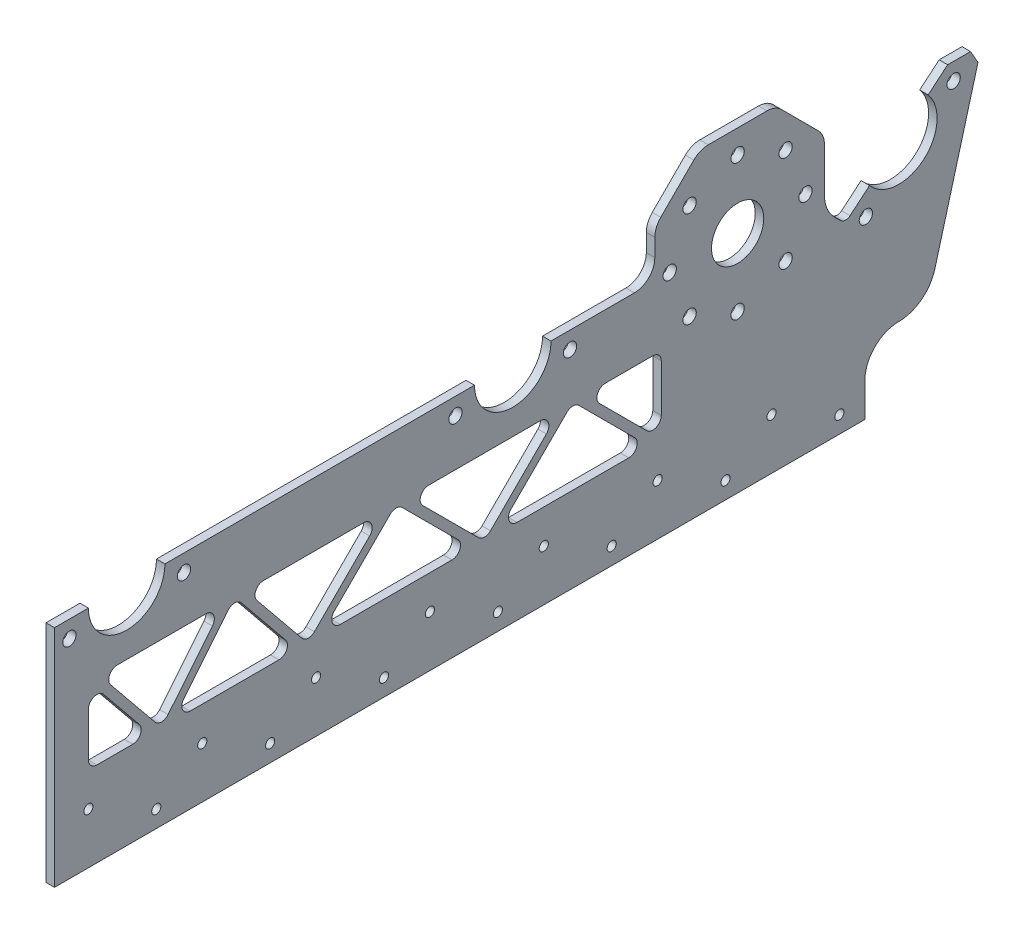
SolidWorks part; units mm, degrees
material "6061 Alloy"
ref_plane "Front Plane" through (0, 0, 0) normal (0, 0, 1) x (1, 0, 0)
ref_plane "Top Plane" through (0, 0, 0) normal (0, 1, 0) x (1, 0, 0)
ref_plane "Right Plane" through (0, 0, 0) normal (1, 0, 0) x (0, 0, -1)
sketch "Sketch1" plane through (0, 0, 0) normal (1, 0, 0) x (0, 0, -1)
  line L0 (-12.7, -12.7) -> (-315.9379, -12.7)
  line L1 (-315.9379, -12.7) -> (-315.9379, 71.4629)
  line L2 (-315.9379, 71.4629) -> (-303.2379, 71.4629)
  line L3 (-274.6121, 71.4629) -> (-158.7754, 71.4629)
  line L5 (10.9643, 80.6631) -> (18.2626, 86.7871)
  line L7 (-315.9379, 12.7) -> (13.4731, 12.7) construction
  line L8 (-12.7, -12.7) -> (-12.7, 0)
  line L9 (0, 12.4079) -> (0, 12.7) construction
  line L10 (13.4731, 22.9772) -> (30.9626, 86.7871)
  line L12 (-10.9643, 62.2627) -> (10.9643, 80.6631) construction
  line L13 (18.2626, 86.7871) -> (30.9626, 86.7871)
  line L14 (-130.1496, 71.4629) -> (-91.313, 71.4629)
  line L15 (-10.9643, 62.2627) -> (-18.2626, 56.1387)
  line L16 (-21.6532, 56.2511) -> (-23.945, 58.4485)
  line L18 (0, 71.4629) -> (-144.4625, 71.4629) construction
  line L19 (-315.9379, 15.875) -> (13.4731, 15.875) construction
  line L20 (-27.8553, 67.6154) -> (-27.8553, 87.307)
  line L21 (-27.8553, 87.307) -> (-46.1742, 105.6259)
  line L22 (-46.1742, 105.6259) -> (-74.4758, 105.6259)
  line L23 (-91.313, 88.7887) -> (-91.313, 71.4629)
  line L25 (-74.4758, 105.6259) -> (-91.313, 88.7887)
  line L26 (-144.4625, 71.4629) -> (-288.925, 71.4629) construction
  arc A3 (0, 12.7) -> (13.4731, 22.9772) centre (0, 26.67) ccw
  arc A4 (0, 12.7) -> (-12.7, 0) centre (0, 0) ccw
  circle A5 centre (0, 0) radius 12.4079 construction
  arc A6 (-303.2379, 71.4629) -> (-274.6121, 71.4629) centre (-288.925, 71.4629) ccw
  arc A7 (-158.7754, 71.4629) -> (-130.1496, 71.4629) centre (-144.4625, 71.4629) ccw
  arc A8 (-10.9643, 62.2627) -> (10.9643, 80.6631) centre (0, 71.4629) ccw
  arc A9 (-18.2626, 56.1387) -> (-21.6532, 56.2511) centre (-19.8953, 58.0845) cw
  circle A11 centre (-60.325, 71.4629) radius 9.779
  arc A14 (-27.8553, 67.6154) -> (-23.945, 58.4485) centre (-15.1553, 67.6154) ccw
  circle A15 centre (-60.325, 71.4629) radius 25.4 construction
  circle A16 centre (-60.325, 96.8629) radius 2.413
  circle A17 centre (-42.3645, 89.4234) radius 2.413
  circle A18 centre (-34.925, 71.4629) radius 2.413
  circle A19 centre (-42.3645, 53.5024) radius 2.413
  circle A20 centre (-60.325, 46.0629) radius 2.413
  circle A21 centre (-78.2855, 53.5024) radius 2.413
  circle A22 centre (-85.725, 71.4629) radius 2.413
  circle A23 centre (-78.2855, 89.4234) radius 2.413
  point P4 (-164.319, -12.7)
  point P44 (-82.018, 71.4629)
  point P51 (-27.8553, 62.1979)
  point P60 (-60.325, 71.4629)
  dimension "D1" = 25.4
  dimension "D3" = 12.7
  dimension "D5" = 28.6258
  dimension "D6" = 3.175
  dimension "D7" = 13.97
  dimension "D8" = 12.7
  dimension "D10" = 24.8158
  dimension "D13" = 9.5273
  dimension "D14" = 140
  dimension "D15" = 2.54
  dimension "D16" = 50.8
  dimension "D17" = 60.325
  dimension "D18" = 41.275
  dimension "D24" = 3.175
  dimension "D26" = 12.7
  dimension "D19" = 4.826
  dimension "D25" = 6.35
  dimension "D29" = 6.35
  dimension "D20" = 4.6567
  dimension "D30" = 9.779
  dimension "D2" = 0
  dimension "D4" = 12.7
  dimension "D9" = 12.7
  dimension "D11" = 288.925
  dimension "D12" = 288.925
  dimension "D21" = 8
  dimension "D22" = 45
  dimension "D23" = 45
  dimension "D27" = 6.35
  dimension "D28" = 3.175
extrude "Boss-Extrude1" add sketch "Sketch1" along normal blind 3.175
hole_wizard "#10 Clearance Hole1" positions "Sketch2" profile "Sketch3" hole size "#10" standard "ANSI Inch" end condition through all
sketch "Sketch2" plane through (3.175, 0, 0) normal (1, 0, 0) x (0, 0, -1)
  line L0 (-310.3562, 65.1129) -> (-267.4937, 65.1129) construction
  line L2 (-165.8937, 65.1129) -> (-123.0313, 65.1129) construction
  line L4 (-12.3356, 52.8228) -> (20.499, 80.3743) construction
  line L6 (-303.2379, 71.4629) -> (-315.9379, 71.4629) construction
  line L7 (-288.925, 65.1129) -> (-288.925, 71.4629) construction
  line L9 (-144.4625, 71.4629) -> (-144.4625, 65.1129) construction
  line L11 (0, 71.4629) -> (4.0817, 66.5985) construction
  line L14 (18.2626, 86.7871) -> (10.9643, 80.6631) construction
  line L15 (18.2626, 86.7871) -> (10.9643, 80.6631) construction
  point P0 (-310.3562, 65.1129)
  point P2 (-267.4937, 65.1129)
  point P4 (-165.8937, 65.1129)
  point P6 (-123.0313, 65.1129)
  point P8 (-12.3356, 52.8228)
  point P10 (20.499, 80.3743)
  dimension "D1" = 42.8625
  dimension "D2" = 6.35
  dimension "D3" = 6.35
sketch "Sketch3" plane through (3.175, 65.1129, 310.3562) normal (0, 1, 0) x (0, 0, -1)
  line L0 (0, 0) -> (0, 3.175)
  line L1 (0, 3.175) -> (2.4892, 3.175)
  line L2 (2.4892, 3.175) -> (2.4892, 0)
  line L5 (2.4892, 0) -> (0, 0)
  line L11 (0, -6.35) -> (0, 107.95) construction
  dimension "Thru Hole Dia." = 4.9784
  dimension "Thru Hole Depth" = 3.175
hole_wizard "#10 Clearance Hole2" positions "Sketch5" profile "Sketch6" hole size "#10" standard "ANSI Inch"
sketch "Sketch5" plane through (3.175, 0, 0) normal (1, 0, 0) x (0, 0, -1)
  point P0 (-60.325, 96.8629)
  point P3 (-42.3645, 89.4234)
  point P6 (-34.925, 71.4629)
  point P9 (-42.3645, 53.5024)
  point P12 (-60.325, 46.0629)
  point P15 (-78.2855, 53.5024)
  point P18 (-85.725, 71.4629)
  point P21 (-78.2855, 89.4234)
sketch "Sketch6" plane through (3.175, 96.8629, 60.325) normal (0, 1, 0) x (0, 0, -1)
  line L0 (0, 0) -> (0, 4.6707)
  line L1 (0, 4.6707) -> (2.4892, 3.175)
  line L2 (2.4892, 3.175) -> (2.4892, 0)
  line L5 (2.4892, 0) -> (0, 0)
  line L10 (0, 4.6707) -> (-2.4892, 3.175) construction
  line L11 (0, -6.35) -> (0, 107.95) construction
  dimension "Hole Dia." = 4.9784
  dimension "Hole Depth" = 3.175
  dimension "Drill Angle" = 118
chamfer "Chamfer1" distance 5.08 angle 45 1 edges at (1.5875, 86.7871, -30.9626) first distance on face at (1.5875, 54.8821, -22.2179)
fillet "Fillet1" radius 7.62 5 edges at (1.5875, 87.307, 27.8553) (1.5875, 105.6259, 46.1742) (1.5875, 105.6259, 74.4758) (1.5875, 88.7887, 91.313) (1.5875, 71.4629, 91.313)
hole_wizard "1/8 (0.135) Diameter Hole1" positions "Sketch7" profile "Sketch8" hole size "1/8" standard "ANSI Inch"
sketch "Sketch7" plane through (0, 0, 0) normal (-1, 0, 0) x (0, 0, 1)
  line L0 (315.9379, -12.7) -> (12.7, -12.7) construction
  line L1 (12.7, -12.7) -> (12.7, 0) construction
  line L2 (315.9379, 71.4629) -> (315.9379, -12.7) construction
  point P0 (22.2504, -6.35)
  point P2 (47.6504, 6.35)
  point P19 (64.8483, -6.35)
  point P20 (90.2483, 6.35)
  point P21 (107.4462, -6.35)
  point P22 (132.8462, 6.35)
  point P23 (150.0441, -6.35)
  point P24 (175.4441, 6.35)
  point P25 (192.6421, -6.35)
  point P26 (218.0421, 6.35)
  point P27 (235.24, -6.35)
  point P28 (260.64, 6.35)
  point P29 (277.8379, -6.35)
  point P30 (303.2379, 6.35)
  dimension "D1" = 6.35
  dimension "D2" = 25.4
  dimension "D3" = 12.7
  dimension "D4" = 9.5504
  dimension "D6" = 12.7
  dimension "D5" = 7
sketch "Sketch8" plane through (0, -6.35, 22.2504) normal (0, 1, 0) x (0, 0, 1)
  line L0 (0, 0) -> (0, 17.5402)
  line L1 (0, 17.5402) -> (1.7145, 16.51)
  line L2 (1.7145, 16.51) -> (1.7145, 0)
  line L5 (1.7145, 0) -> (0, 0)
  line L10 (0, 17.5402) -> (-1.7145, 16.51) construction
  line L11 (0, -6.35) -> (0, 107.95) construction
  dimension "Hole Dia." = 3.429
  dimension "Hole Depth" = 16.51
  dimension "Drill Angle" = 118
sketch "Sketch9" plane through (3.175, 0, 0) normal (1, 0, 0) x (0, 0, -1)
  line L0 (-303.2379, 47.625) -> (-303.2379, 19.05)
  line L1 (-303.2379, 19.05) -> (-279.973, 19.05)
  line L2 (-279.973, 19.05) -> (-303.2379, 47.625)
  line L3 (-315.9379, 12.7) -> (-12.7, 12.7) construction
  line L4 (-315.9379, 15.875) -> (-12.7, 15.875) construction
  line L5 (-299.1437, 47.625) -> (-275.8788, 19.05)
  line L6 (-275.8788, 19.05) -> (-252.6139, 47.625)
  line L7 (-252.6139, 47.625) -> (-299.1437, 47.625)
  line L8 (-271.7845, 19.05) -> (-248.5196, 47.625)
  line L9 (-248.5196, 47.625) -> (-225.2548, 19.05)
  line L10 (-225.2548, 19.05) -> (-271.7845, 19.05)
  line L11 (-244.4254, 47.625) -> (-221.1605, 19.05)
  line L12 (-221.1605, 19.05) -> (-192.5855, 47.625)
  line L13 (-192.5855, 47.625) -> (-244.4254, 47.625)
  line L14 (-216.6704, 19.05) -> (-188.0954, 47.625)
  line L15 (-188.0954, 47.625) -> (-159.5204, 19.05)
  line L16 (-159.5204, 19.05) -> (-216.6704, 19.05)
  line L17 (-183.6053, 47.625) -> (-155.0303, 19.05)
  line L18 (-155.0303, 19.05) -> (-126.4553, 47.625)
  line L19 (-126.4553, 47.625) -> (-183.6053, 47.625)
  line L20 (-121.9651, 47.625) -> (-150.5401, 19.05)
  line L21 (-150.5401, 19.05) -> (-93.3901, 19.05)
  line L22 (-93.3901, 19.05) -> (-121.9651, 47.625)
  line L32 (-315.9379, -12.7) -> (-12.7, -12.7) construction
  line L33 (-315.9379, 71.4629) -> (-315.9379, -12.7) construction
  line L35 (-117.475, 47.625) -> (-88.9, 19.05)
  line L36 (-88.9, 19.05) -> (-88.9, 47.625)
  line L37 (-88.9, 47.625) -> (-117.475, 47.625)
  line L38 (-12.7, -12.7) -> (-12.7, 0) construction
  arc A0 (-303.2379, 71.4629) -> (-274.6121, 71.4629) centre (-288.925, 71.4629) ccw construction
  point P28 (0, 0)
  dimension "D1" = 3.175
  dimension "D2" = 3.175
  dimension "D3" = 3.175
  dimension "D4" = 3.175
  dimension "D5" = 3.175
  dimension "D6" = 3.175
  dimension "D7" = 3.175
  dimension "D8" = 76.2
  dimension "D9" = 3.175
  dimension "D11" = 25.4
  dimension "D12" = 3.175
  dimension "D13" = 12.7
  dimension "D15" = 9.525
extrude "Cut-Extrude1" cut sketch "Sketch9" against normal through all
fillet "Fillet2" radius 3.175 24 edges at (1.5875, 19.05, 303.2379) (1.5875, 47.625, 303.2379) (1.5875, 19.05, 279.973) (1.5875, 19.05, 150.5401) (1.5875, 47.625, 121.9651) (1.5875, 19.05, 93.3901) (1.5875, 19.05, 155.0303) (1.5875, 47.625, 183.6053) (1.5875, 47.625, 126.4553) (1.5875, 19.05, 88.9) (1.5875, 47.625, 117.475) (1.5875, 47.625, 88.9) (1.5875, 47.625, 248.5196) (1.5875, 19.05, 225.2548) (1.5875, 19.05, 271.7845) (1.5875, 19.05, 275.8788) (1.5875, 47.625, 299.1437) (1.5875, 47.625, 252.6139) (1.5875, 19.05, 159.5204) (1.5875, 19.05, 216.6704) (1.5875, 19.05, 221.1605) (1.5875, 47.625, 244.4254) (1.5875, 47.625, 192.5855) (1.5875, 47.625, 188.0954)
